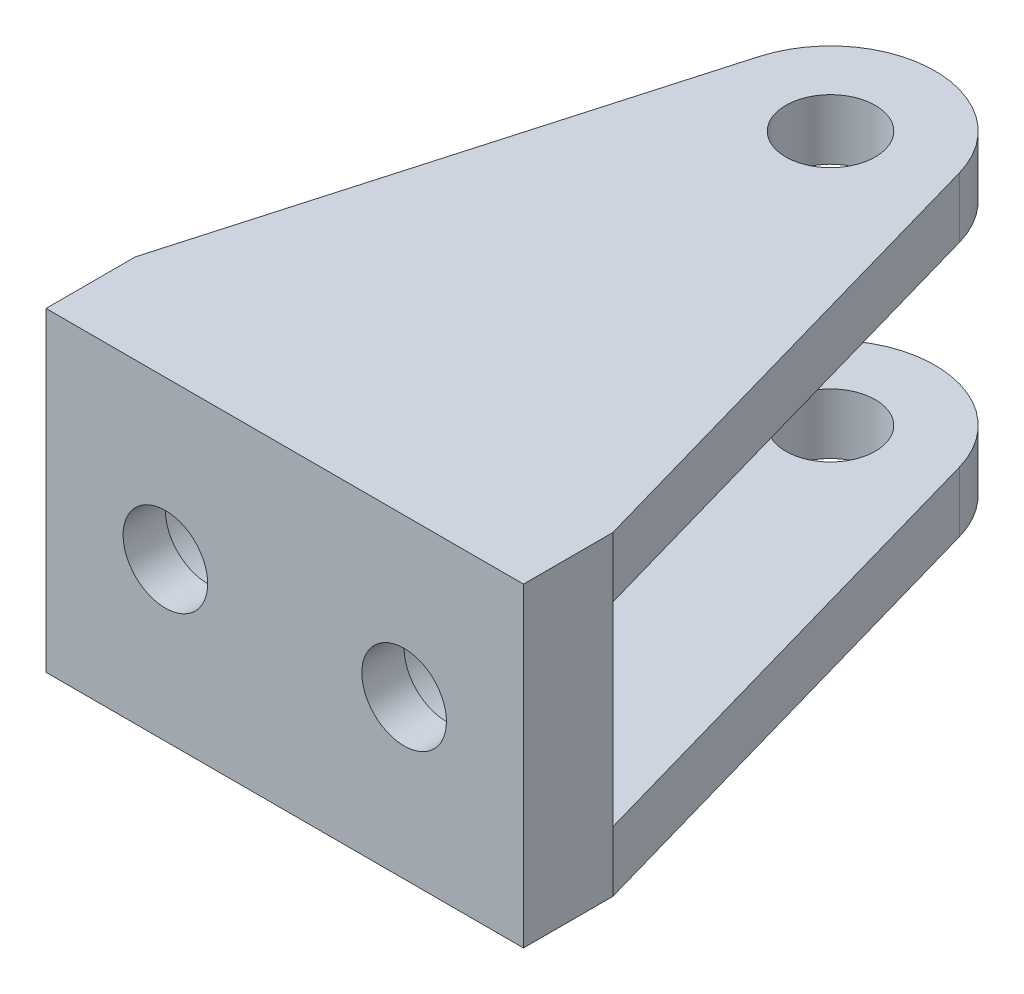
SolidWorks part; units mm, degrees
ref_plane "Front Plane" through (0, 0, 0) normal (0, 0, 1) x (1, 0, 0)
ref_plane "Top Plane" through (0, 0, 0) normal (0, 1, 0) x (1, 0, 0)
ref_plane "Right Plane" through (0, 0, 0) normal (1, 0, 0) x (0, 0, -1)
sketch "Sketch1" plane through (0, 0, 0) normal (0, 1, 0) x (1, 0, 0)
  line L0 (0, 0) -> (50.8, 0)
  line L1 (50.8, 0) -> (50.8, 9.4996)
  line L2 (0, 0) -> (0, 9.4996)
  line L3 (50.8, 9.4996) -> (36.0867, 61.111)
  line L4 (0, 9.4996) -> (14.7133, 61.111)
  line L5 (25.4, 0) -> (25.4, 43.8119) construction
  circle A0 centre (25.4, 58.0644) radius 4.7625
  arc A1 (36.0867, 61.111) -> (14.7133, 61.111) centre (25.4, 58.0644) ccw
  dimension "D4" = 6.35
  dimension "D5" = 9.525
  dimension "D1" = 58.0644
  dimension "D2" = 50.8
  dimension "D3" = 9.4996
extrude "Boss-Extrude1" add sketch "Sketch1" along normal blind 33.528
sketch "Sketch2" plane through (50.8, 0, 0) normal (1, 0, 0) x (0, 0, -1)
  line L0 (9.4996, 16.764) -> (9.4996, 27.1145)
  line L1 (9.4996, 33.528) -> (9.4996, 0) construction
  line L2 (9.4996, 27.1145) -> (69.1769, 27.1145)
  line L3 (9.4996, 16.764) -> (9.4996, 6.4135)
  line L4 (9.4996, 6.4135) -> (69.1769, 6.4135)
  line L5 (69.1769, 6.4135) -> (69.1769, 27.1145)
  line L6 (69.1769, 0) -> (69.1769, 33.528) construction
  dimension "D1" = 20.701
extrude "Cut-Extrude1" cut sketch "Sketch2" against normal through all
sketch "Sketch3" plane through (0, 0, -9.4996) normal (0, 0, -1) x (-1, 0, 0)
  line L0 (-50.8, 16.764) -> (0, 16.764) construction
  line L1 (-50.8, 27.1145) -> (-50.8, 6.4135) construction
  line L2 (0, 27.1145) -> (0, 6.4135) construction
  line L3 (-25.4, 16.764) -> (-25.4, 27.1145) construction
  line L4 (0, 27.1145) -> (-50.8, 27.1145) construction
  point P10 (-38.1, 16.764)
  point P11 (-12.7, 16.764)
  dimension "D1" = 12.7
  dimension "D2" = 25.4
hole_wizard "CBORE for M8 Hex Head Bolt1" positions "Sketch3" profile "Sketch4" counterbore size "M8" standard "ANSI Metric" end condition through all
sketch "Sketch4" plane through (12.7, 16.764, -9.4996) normal (1, 0, 0) x (0, 1, 0)
  line L0 (0, 0) -> (0, 9.4996)
  line L1 (0, 9.4996) -> (4.5, 9.4996)
  line L3 (4.5, 9.4996) -> (4.5, 5)
  line L4 (4.5, 5) -> (8, 5)
  line L5 (8, 5) -> (8, 0)
  line L7 (8, 0) -> (0, 0)
  line L11 (0, -6.35) -> (0, 107.95) construction
  dimension "Thru Hole Dia." = 9
  dimension "Thru Hole Depth" = 9.4996
  dimension "C'Bore Dia." = 16
  dimension "C'Bore Depth" = 5
equation "\"1inch\"=62.1211"
